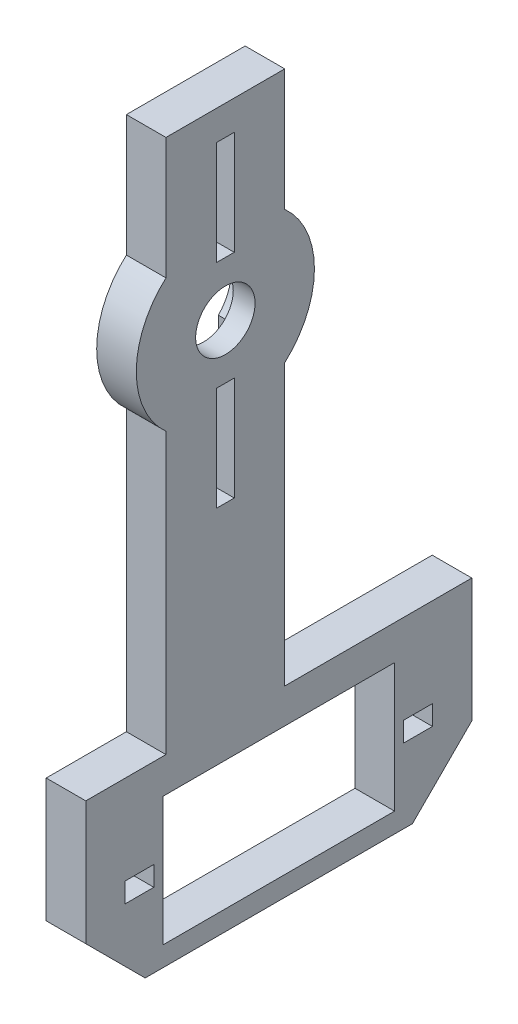
SolidWorks part; units mm, degrees
ref_plane "Front Plane" through (0, 0, 0) normal (0, 0, 1) x (1, 0, 0)
ref_plane "Top Plane" through (0, 0, 0) normal (0, 1, 0) x (1, 0, 0)
ref_plane "Right Plane" through (0, 0, 0) normal (1, 0, 0) x (0, 0, -1)
sketch "Sketch1" plane through (0, 0, 0) normal (1, 0, 0) x (0, 0, -1)
  circle A0 centre (-66, -20) radius 9
extrude "Boss-Extrude1" add sketch "Sketch1" along normal blind 4 from offset 66.4
sketch "Sketch2" plane through (0, 0, 0) normal (0, 0, 1) x (1, 0, 0)
  line L1 (66.4, -56) -> (70.4, -56)
  line L2 (66.4, -56) -> (66.4, -1)
  line L3 (66.4, -1) -> (70.4, -1)
  line L4 (70.4, -56) -> (70.4, -1)
extrude "Boss-Extrude2" add sketch "Sketch2" along normal blind 12 from offset 60
sketch "Sketch3" plane through (0, 0, 0) normal (0, 0, 1) x (1, 0, 0)
  line L1 (66.4, -73.5) -> (70.4, -73.5)
  line L2 (66.4, -73.5) -> (66.4, -55)
  line L3 (66.4, -55) -> (70.4, -55)
  line L4 (70.4, -73.5) -> (70.4, -55)
extrude "Boss-Extrude3" add sketch "Sketch3" along normal blind 39 from offset 41.1
sketch "Sketch4" plane through (0, 0, 0) normal (1, 0, 0) x (0, 0, -1)
  line L0 (-81.1, -74.5) -> (-73.1, -74.5)
  line L1 (-73.1, -74.5) -> (-81.1, -66.5)
  line L2 (-81.1, -66.5) -> (-81.1, -74.5)
extrude "Boss-Extrude4" add sketch "Sketch4" along normal blind 6 from offset 65.4 separate body
combine bodies "Combine1" operation type subtract main body 103 bodies to subtract 104
sketch "Sketch5" plane through (0, 0, 0) normal (1, 0, 0) x (0, 0, -1)
  line L0 (-40.1, -74.5) -> (-48.1, -74.5)
  line L1 (-48.1, -74.5) -> (-40.1, -66.5)
  line L2 (-40.1, -66.5) -> (-40.1, -74.5)
extrude "Boss-Extrude5" add sketch "Sketch5" along normal blind 6 from offset 65.4 separate body
combine bodies "Combine2" operation type subtract main body 105 bodies to subtract 106
sketch "Sketch6" plane through (0, 0, 0) normal (1, 0, 0) x (0, 0, -1)
  circle A0 centre (-66, -20) radius 4.6
extrude "Boss-Extrude6" add sketch "Sketch6" along normal blind 2.3 from offset 65.9 separate body
combine bodies "Combine3" operation type subtract main body 107 bodies to subtract 108
sketch "Sketch7" plane through (0, 0, 0) normal (0, 0, 1) x (1, 0, 0)
  line L1 (65.9, -20) -> (68.2, -20)
  line L2 (65.9, -20) -> (65.9, -2.5)
  line L3 (65.9, -2.5) -> (68.2, -2.5)
  line L4 (68.2, -20) -> (68.2, -2.5)
extrude "Boss-Extrude7" add sketch "Sketch7" along normal blind 6.6 from offset 62.7 separate body
combine bodies "Combine4" operation type subtract main body 109 bodies to subtract 110
sketch "Sketch8" plane through (0, 0, 0) normal (0, 0, 1) x (1, 0, 0)
  line L1 (65.4, -14.5) -> (71.4, -14.5)
  line L2 (65.4, -14.5) -> (65.4, -4)
  line L3 (65.4, -4) -> (71.4, -4)
  line L4 (71.4, -14.5) -> (71.4, -4)
extrude "Boss-Extrude8" add sketch "Sketch8" along normal blind 1.8 from offset 65.1 separate body
combine bodies "Combine5" operation type subtract main body 111 bodies to subtract 112
sketch "Sketch9" plane through (0, 0, 0) normal (0, 0, 1) x (1, 0, 0)
  line L1 (65.9, -37.5) -> (68.2, -37.5)
  line L2 (65.9, -37.5) -> (65.9, -20)
  line L3 (65.9, -20) -> (68.2, -20)
  line L4 (68.2, -37.5) -> (68.2, -20)
extrude "Boss-Extrude9" add sketch "Sketch9" along normal blind 6.6 from offset 62.7 separate body
combine bodies "Combine6" operation type subtract main body 113 bodies to subtract 114
sketch "Sketch10" plane through (0, 0, 0) normal (0, 0, 1) x (1, 0, 0)
  line L1 (65.4, -36) -> (71.4, -36)
  line L2 (65.4, -36) -> (65.4, -25.5)
  line L3 (65.4, -25.5) -> (71.4, -25.5)
  line L4 (71.4, -36) -> (71.4, -25.5)
extrude "Boss-Extrude10" add sketch "Sketch10" along normal blind 1.8 from offset 65.1 separate body
combine bodies "Combine7" operation type subtract main body 115 bodies to subtract 116
sketch "Sketch11" plane through (0, 0, 0) normal (1, 0, 0) x (0, 0, -1)
  circle A0 centre (-66, -20) radius 3
extrude "Boss-Extrude11" add sketch "Sketch11" along normal blind 6 from offset 65.4 separate body
combine bodies "Combine8" operation type subtract main body 117 bodies to subtract 118
sketch "Sketch12" plane through (0, 0, 0) normal (0, 0, 1) x (1, 0, 0)
  line L1 (65.4, -71.5) -> (71.4, -71.5)
  line L2 (65.4, -71.5) -> (65.4, -58.5)
  line L3 (65.4, -58.5) -> (71.4, -58.5)
  line L4 (71.4, -71.5) -> (71.4, -58.5)
extrude "Boss-Extrude12" add sketch "Sketch12" along normal blind 23.4 from offset 48.9 separate body
combine bodies "Combine9" operation type subtract main body 119 bodies to subtract 120
sketch "Sketch13" plane through (0, 0, 0) normal (0, 0, 1) x (1, 0, 0)
  line L1 (65.4, -66) -> (71.4, -66)
  line L2 (65.4, -66) -> (65.4, -64)
  line L3 (65.4, -64) -> (71.4, -64)
  line L4 (71.4, -66) -> (71.4, -64)
extrude "Boss-Extrude13" add sketch "Sketch13" along normal blind 2.9 from offset 45.075 separate body
combine bodies "Combine10" operation type subtract main body 121 bodies to subtract 122
sketch "Sketch14" plane through (0, 0, 0) normal (0, 0, 1) x (1, 0, 0)
  line L1 (65.4, -66) -> (71.4, -66)
  line L2 (65.4, -66) -> (65.4, -64)
  line L3 (65.4, -64) -> (71.4, -64)
  line L4 (71.4, -66) -> (71.4, -64)
extrude "Boss-Extrude14" add sketch "Sketch14" along normal blind 2.9 from offset 73.225 separate body
combine bodies "Combine11" operation type subtract main body 123 bodies to subtract 124
